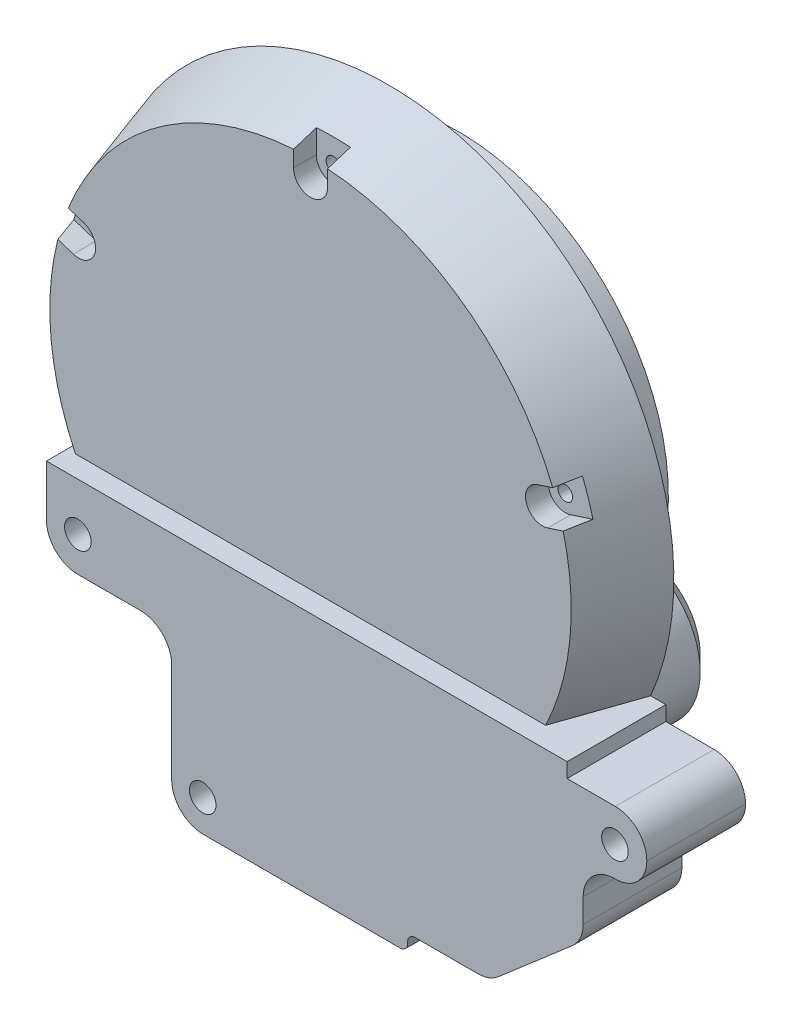
SolidWorks part; units mm, degrees
ref_plane "Front Plane" through (0, 0, 0) normal (0, 0, 1) x (1, 0, 0)
ref_plane "Top Plane" through (0, 0, 0) normal (0, 1, 0) x (1, 0, 0)
ref_plane "Right Plane" through (0, 0, 0) normal (1, 0, 0) x (0, 0, -1)
sketch "Sketch1" plane through (0, 0, 0) normal (0, 0, 1) x (1, 0, 0)
  circle A0 centre (0, 0) radius 98.2726
  dimension "D1" = 196.5452
extrude "Extrude1" add sketch "Sketch1" along normal blind 26.8732 draft 17.5
sketch "Sketch2" plane through (0, 0, 26.8732) normal (0, 0, 1) x (1, 0, 0)
  line L0 (-79.8887, 25.9574) -> (0, 0) construction
  line L1 (0, 0) -> (0, 83.9978) construction
  line L3 (0, 0) -> (79.8887, 25.9574) construction
  circle A0 centre (0, 83.9978) radius 2.5
  circle A2 centre (-79.8887, 25.9574) radius 2.5
  circle A3 centre (79.8887, 25.9574) radius 2.5
  circle A4 centre (0, 0) radius 84 construction
  dimension "D2" = 5
  dimension "D3" = 72
  dimension "D5" = 168
  dimension "D1" = 83.9978
extrude "Extrude2" cut sketch "Sketch2" against normal offset from surface (22.8854 mm away) 3.9878 up to face at (98.2726, 0, 0)
sketch "Sketch3" plane through (0, 0, 26.8732) normal (0, 0, 1) x (1, 0, 0)
  line L0 (-5.8547, 83.9978) -> (-5.8547, 107.0835)
  line L1 (-5.8547, 107.0835) -> (5.8547, 107.0835)
  line L2 (5.8547, 107.0835) -> (5.8547, 83.9978)
  line L3 (0, 0) -> (79.8887, 25.9574) construction
  line L4 (-79.8887, 25.9574) -> (0, 0) construction
  line L5 (78.0795, 31.5256) -> (107.5199, 41.0913)
  line L7 (81.6979, 20.3893) -> (111.1362, 29.9544)
  line L8 (111.1362, 29.9544) -> (110.1407, 33.9126)
  line L9 (107.5199, 41.0913) -> (110.1407, 33.9126)
  line L10 (-78.0795, 31.5256) -> (-100.2418, 38.7265)
  line L11 (-100.2418, 38.7265) -> (-103.8602, 27.5902)
  line L13 (-81.6979, 20.3893) -> (-103.8602, 27.5902)
  arc A0 (-5.8547, 83.9978) -> (5.8547, 83.9978) centre (0, 83.9978) ccw
  arc A1 (78.0795, 31.5256) -> (81.6979, 20.3893) centre (79.8887, 25.9574) ccw
  arc A2 (-81.6979, 20.3893) -> (-78.0795, 31.5256) centre (-79.8887, 25.9574) ccw
  dimension "D1" = 11.7094
  dimension "D2" = 11.7094
  dimension "D3" = 11.7094
extrude "Extrude3" cut sketch "Sketch3" against normal offset from surface (7.874 mm away) 18.9992 up to face at (98.2726, 0, 0)
sketch "Sketch4" plane through (0, 0, 26.8732) normal (0, 0, 1) x (1, 0, 0)
  line L1 (-114.267, -38.8366) -> (132.694, -38.8366)
  line L2 (-114.267, -38.8366) -> (-114.267, -123.19)
  line L3 (-114.267, -123.19) -> (132.694, -123.19)
  line L4 (132.694, -38.8366) -> (132.694, -123.19)
  arc A0 (83.4135, 33.2587) -> (5.8547, 89.6085) centre (0, 0) ccw construction
  dimension "D1" = 38.8366
  dimension "D2" = 84.3534
extrude "Extrude4" add sketch "Sketch4" along normal offset from surface 34.0106 and the other way up to surface (26.8732 mm away) up to face at (98.2726, 0, 0) other way up to face at (98.2726, 0, 0)
sketch "Sketch5" plane through (0, 0, 34.0106) normal (0, 0, 1) x (1, 0, 0)
  line L0 (132.694, -38.8366) -> (-114.267, -38.8366) construction
  line L1 (-83.82, -67.2338) -> (-40.6908, -67.2338)
  line L2 (-133.7303, -141.5321) -> (-133.7303, -176.3152)
  line L3 (-133.7303, -176.3152) -> (-40.6908, -176.3152)
  line L4 (-40.6908, -67.2338) -> (-40.6908, -176.3152)
  line L6 (-175.2407, -38.8366) -> (-83.82, -38.8366)
  line L7 (-175.2407, -38.8366) -> (-175.2407, -141.5321)
  line L8 (-175.2407, -141.5321) -> (-133.7303, -141.5321)
  line L9 (-83.82, -38.8366) -> (-83.82, -67.2338)
  arc A0 (90.273, -38.8366) -> (-90.273, -38.8366) centre (0, 0) ccw construction
  dimension "D1" = 28.3972
  dimension "D2" = 40.6908
  dimension "D3" = 43.1292
extrude "Extrude5" cut sketch "Sketch5" against normal blind 34.0106
sketch "Sketch6" plane through (0, 0, 34.0106) normal (0, 0, 1) x (1, 0, 0)
  line L0 (-40.6908, -123.19) -> (132.694, -123.19) construction
  line L1 (40.5892, -117.475) -> (68.7832, -117.475)
  line L2 (40.5892, -117.475) -> (40.5892, -172.463)
  line L3 (40.5892, -172.463) -> (68.7832, -172.463)
  line L4 (122.9614, -43.8912) -> (122.9614, -65.5574)
  line L5 (68.7832, -117.475) -> (101.0412, -89.6112)
  line L6 (68.7832, -172.463) -> (148.3735, -172.463)
  line L7 (122.9614, 0) -> (187.2412, 0)
  line L8 (101.0412, -89.6112) -> (101.0412, -65.5574)
  line L9 (101.0412, -65.5574) -> (122.9614, -65.5574)
  line L10 (148.3735, -112.1723) -> (148.3735, -89.6112)
  line L11 (148.3735, -172.463) -> (148.3735, -112.1723)
  line L12 (132.694, -38.8366) -> (-83.82, -38.8366) construction
  line L13 (95.504, -38.8366) -> (122.9614, -38.8366)
  line L14 (95.504, -38.8366) -> (95.504, -43.8912)
  line L15 (95.504, -43.8912) -> (122.9614, -43.8912)
  line L17 (122.9614, 0) -> (122.9614, -38.8366)
  line L18 (148.3735, -89.6112) -> (187.2412, -89.6112)
  line L19 (187.2412, 0) -> (187.2412, -89.6112)
  arc A0 (90.273, -38.8366) -> (-90.273, -38.8366) centre (0, 0) ccw construction
  dimension "D1" = 5.715
  dimension "D2" = 40.5892
  dimension "D3" = 28.194
  dimension "D4" = 32.258
  dimension "D5" = 27.8638
  dimension "D6" = 21.6662
  dimension "D7" = 5.0546
  dimension "D8" = 95.504
  dimension "D9" = 122.9614
extrude "Extrude6" cut sketch "Sketch6" against normal blind 34.0106
sketch "Sketch8" plane through (0, 0, 0) normal (0, 0, -1) x (-1, 0, 0)
  circle A0 centre (0, -79.0956) radius 25.7175
  circle A1 centre (-47.7266, -57.0992) radius 25.7175
  dimension "D2" = 51.435
  dimension "D3" = 51.435
  dimension "D1" = 79.0956
  dimension "D4" = 47.7266
  dimension "D5" = 21.9964
extrude "Extrude7" add sketch "Sketch8" along normal blind 38.989
sketch "Sketch9" plane through (0, 0, 0) normal (0, 0, -1) x (-1, 0, 0)
  circle A0 centre (0, 0) radius 79.248
  dimension "D1" = 158.496
extrude "Extrude9" add sketch "Sketch9" along normal blind 9.6012
sketch "Sketch10" plane through (0, 0, -9.6012) normal (0, 0, -1) x (-1, 0, 0)
  circle A0 centre (0, 0) radius 72.39
  dimension "D1" = 144.78
extrude "Extrude10" add sketch "Sketch10" along normal blind 14.4018
sketch "Sketch11" plane through (0, 0, -24.003) normal (0, 0, -1) x (-1, 0, 0)
  circle A0 centre (0, 0) radius 37.592
  dimension "D1" = 75.184
extrude "Extrude11" add sketch "Sketch11" along normal blind 18.9992
sketch "Sketch12" plane through (0, 0, -43.0022) normal (0, 0, -1) x (-1, 0, 0)
  circle A0 centre (0, 0) radius 13.9065
  dimension "D1" = 27.813
extrude "Extrude12" cut sketch "Sketch12" against normal blind 21.717
sketch "Sketch13" plane through (0, 0, 0) normal (0, 0, -1) x (-1, 0, 0)
  line L0 (-58.4911, -80.4555) -> (-10.7645, -102.4519)
  line L3 (10.7645, -55.7393) -> (-36.9621, -33.7429)
  circle A0 centre (-47.7266, -57.0992) radius 25.7175 construction
  arc A1 (-25.4, -75.0672) -> (25.4, -75.0672) centre (0, -79.0956) ccw construction
  arc A2 (23.4303, -68.4933) -> (-23.4303, -68.4933) centre (0, -79.0956) ccw construction
  arc A3 (-24.4908, -68.1213) -> (-62.696, -36.1873) centre (-47.7266, -57.0992) ccw construction
  circle A4 centre (0, -79.0956) radius 25.7175 construction
  arc A5 (-10.7645, -102.4519) -> (10.7645, -55.7393) centre (0, -79.0956) ccw
  arc A6 (-36.9621, -33.7429) -> (-58.4911, -80.4555) centre (-47.7266, -57.0992) ccw
extrude "Extrude13" add sketch "Sketch13" along normal blind 22.4028
chamfer "Chamfer1" distance 5.08 angle 45 2 edges at (-25.7175, -79.0956, -38.989) (22.0091, -57.0992, -38.989)
fillet "Fillet1" radius 10.8331 8 edges at (122.9614, -65.5574, 17.0053) (122.9614, -43.8912, 17.0053) (101.0412, -65.5574, 17.0053) (101.0412, -89.6112, 17.0053) (68.7832, -117.475, 17.0053) (-40.6908, -67.2338, 17.0053) (-40.6908, -123.19, 17.0053) (-83.82, -67.2338, 17.0053)
fillet "Fillet2" radius 2.54 2 edges at (40.5892, -117.475, 17.0053) (40.5892, -123.19, 17.0053)
sketch "Sketch17" plane through (0, 0, 34.0106) normal (0, 0, 1) x (1, 0, 0)
  line L0 (-72.9996, -55.2958) -> (112.0004, -55.2958) construction
  line L1 (-72.9996, -55.2958) -> (-29.9996, -112.2958) construction
  line L2 (-29.9996, -112.2958) -> (112.0004, -55.2958) construction
  arc A1 (83.4135, 33.2587) -> (5.8547, 89.6085) centre (0, 0) ccw construction
  circle A2 centre (-72.9996, -55.2958) radius 4.572
  circle A3 centre (112.0004, -55.2958) radius 4.572
  circle A4 centre (-29.9996, -112.2958) radius 4.572
  dimension "D3" = 9.144
  dimension "D4" = 9.144
  dimension "D5" = 9.144
  dimension "D1" = 72.9996
  dimension "D2" = 55.2958
extrude "Extrude14" cut sketch "Sketch17" against normal through all
sketch "Sketch18" plane through (0, 0, -43.0022) normal (0, 0, -1) x (-1, 0, 0)
  circle A0 centre (0, 0) radius 19.05
  circle A1 centre (0, 0) radius 13.9065
  dimension "D1" = 38.1
extrude "Extrude15" add sketch "Sketch18" along normal blind 3.2639
